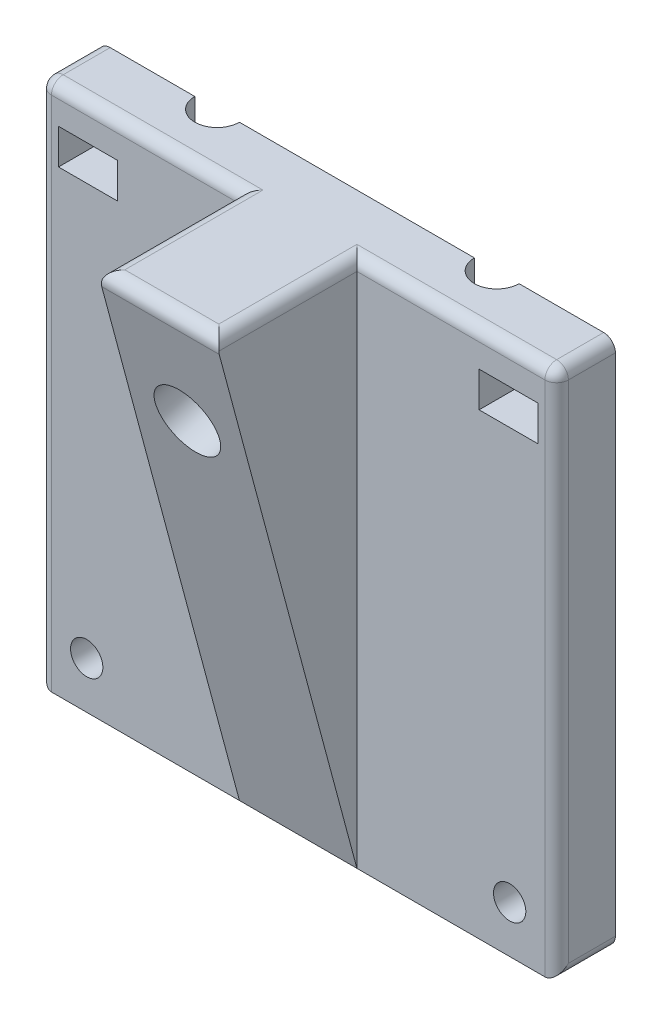
SolidWorks part; units mm, degrees
ref_plane "Front Plane" through (0, 0, 0) normal (0, 0, 1) x (1, 0, 0)
ref_plane "Top Plane" through (0, 0, 0) normal (0, 1, 0) x (1, 0, 0)
ref_plane "Right Plane" through (0, 0, 0) normal (1, 0, 0) x (0, 0, -1)
sketch "Sketch1" plane through (0, 0, 0) normal (0, 0, 1) x (1, 0, 0)
  line L1 (-22, 22.5) -> (22, 22.5)
  line L2 (-22, 22.5) -> (-22, -22.5)
  line L3 (-22, -22.5) -> (22, -22.5)
  line L4 (22, 22.5) -> (22, -22.5)
  line L5 (-22, 22.5) -> (22, -22.5) construction
  line L6 (-22, -22.5) -> (22, 22.5) construction
  point P0 (0, 0)
  dimension "D1" = 44
  dimension "D2" = 45
extrude "Base" add sketch "Sketch1" along normal blind 5
sketch "Sketch2" plane through (0, 22.5, 0) normal (0, 1, 0) x (1, 0, 0)
  line L0 (22, 0) -> (-22, 0) construction
  line L1 (-13.8, 0) -> (-10, 0)
  line L2 (0, 0) -> (0, -5) construction
  line L3 (22, -5) -> (-22, -5) construction
  line L4 (13.8, 0) -> (10, 0)
  arc A0 (-13.8, 0) -> (-10, 0) centre (-11.9, 0) ccw
  arc A1 (13.8, 0) -> (10, 0) centre (11.9, 0) cw
  dimension "D1" = 1.9
  dimension "D2" = 11.9
extrude "Wire Grooves" cut sketch "Sketch2" against normal through all
sketch "Sketch4" plane through (22, 0, 0) normal (1, 0, 0) x (0, 0, -1)
  line L0 (-5, -22.5) -> (-5, 22.5)
  line L1 (-5, -22.5) -> (-17.0577, 22.5)
  line L2 (-17.0577, 22.5) -> (-5, 22.5)
  dimension "D1" = 15
extrude "Slanted Screw Platform" add sketch "Sketch4" against normal mid plane 10 from surface starting at plane "Right Plane"
sketch "Sketch5" plane through (0, -2.7572, 10.2901) normal (0, -0.2588, 0.9659) x (1, 0, 0)
  line L0 (0, 0) -> (0, 26.1482) construction
  line L1 (-5, 26.1482) -> (5, 26.1482) construction
  circle A0 centre (0, 16) radius 2.75
  dimension "D1" = 5.5
  dimension "D2" = 16
extrude "Mounting Hole Screw Insertion" cut sketch "Sketch5" against normal through all
sketch "Sketch6" plane through (0, 0, 5) normal (0, 0, 1) x (1, 0, 0)
  line L0 (0, 22.5) -> (0, -22.5) construction
  line L1 (-5, 22.5) -> (5, 22.5) construction
  line L2 (-5, -22.5) -> (5, -22.5) construction
  line L3 (-22, 22.5) -> (-22, -22.5) construction
  line L4 (-20.4, 19.5) -> (-15.4, 19.5)
  line L5 (-20.4, 19.5) -> (-20.4, 16.5)
  line L6 (-20.4, 16.5) -> (-15.4, 16.5)
  line L7 (-15.4, 19.5) -> (-15.4, 16.5)
  line L8 (20.4, 16.5) -> (15.4, 16.5)
  line L9 (15.4, 19.5) -> (15.4, 16.5)
  line L10 (20.4, 19.5) -> (15.4, 19.5)
  line L11 (20.4, 19.5) -> (20.4, 16.5)
  point P10 (-17.9, 19.5)
  dimension "D1" = 5
  dimension "D2" = 3
  dimension "D3" = 3
  dimension "D4" = 4.1
extrude "Zip Tie Slots" cut sketch "Sketch6" against normal through all
sketch "Sketch7" plane through (0, 0, 5) normal (0, 0, 1) x (1, 0, 0)
  line L0 (-22, 22.5) -> (-22, -22.5) construction
  line L1 (-22, -22.5) -> (-5, -22.5) construction
  line L2 (0, 22.5) -> (0, -22.5) construction
  line L3 (-5, 22.5) -> (5, 22.5) construction
  line L4 (-5, -22.5) -> (5, -22.5) construction
  circle A0 centre (-18, -18.5) radius 1.375
  circle A1 centre (18, -18.5) radius 1.375
  dimension "D1" = 2.75
  dimension "D2" = 4
  dimension "D3" = 4
extrude "Mount Clamping Holes" cut sketch "Sketch7" against normal through all
fillet "Edge Fillets" radius 1 11 edges at (22, 0, 5) (-5, 22.5, 11.0289) (0, 22.5, 17.0577) (5, 22.5, 11.0289) (13.5, 22.5, 5) (-22, 0, 5) (-13.5, 22.5, 5) (22, -22.5, 2.5) (-22, -22.5, 2.5) (22, 22.5, 2.5) (-22, 22.5, 2.5)
